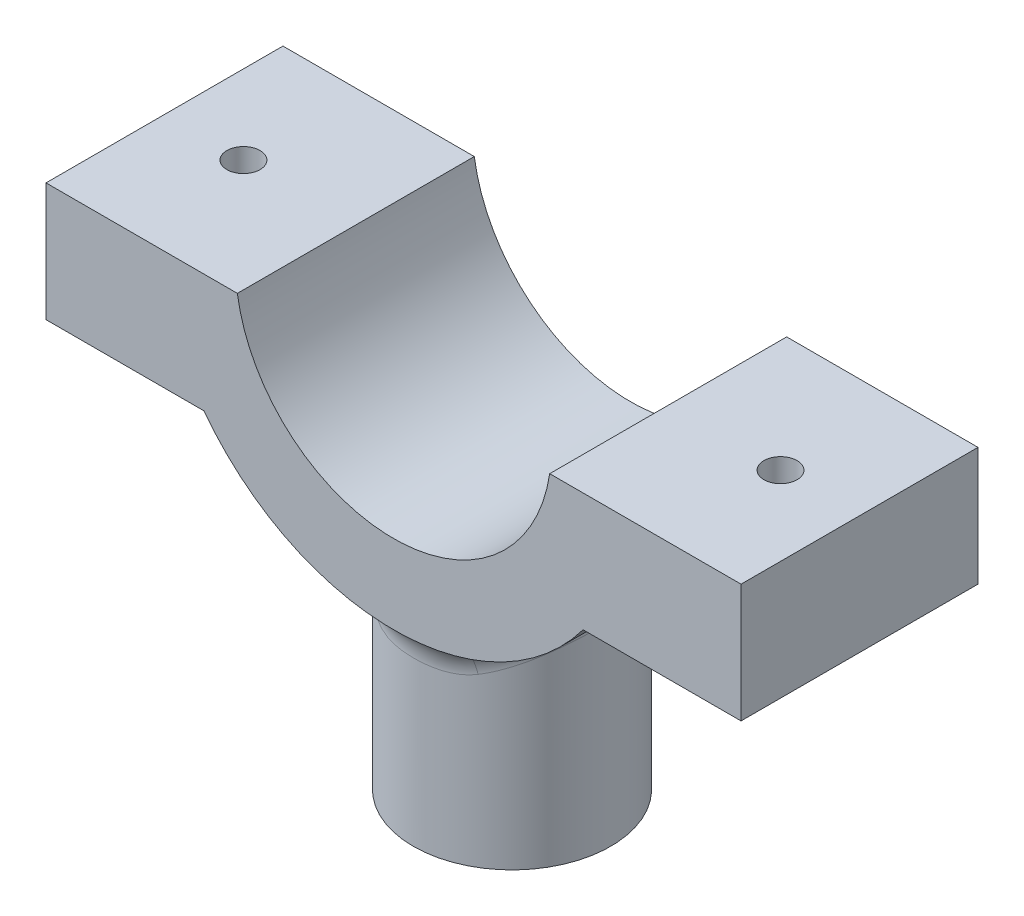
SolidWorks part; units mm, degrees
ref_plane "Plan de face" through (0, 0, 0) normal (0, 0, 1) x (1, 0, 0)
ref_plane "Plan de dessus" through (0, 0, 0) normal (0, 1, 0) x (1, 0, 0)
ref_plane "Plan de droite" through (0, 0, 0) normal (1, 0, 0) x (0, 0, -1)
sketch "Esquisse1" plane through (0, 0, 0) normal (0, 0, 1) x (1, 0, 0)
  line L0 (-19.7737, -3) -> (-44, -3)
  line L1 (-44, -3) -> (-44, -18)
  line L2 (-44, -18) -> (-24, -18)
  line L3 (19.7737, -3) -> (44, -3)
  line L4 (44, -3) -> (44, -18)
  line L5 (44, -18) -> (24, -18)
  line L8 (-44, 3) -> (-44, 18) construction
  line L9 (44, 3) -> (44, 18) construction
  arc A0 (-19.7737, -3) -> (19.7737, -3) centre (0, 0) ccw
  arc A1 (-24, -18) -> (24, -18) centre (0, 0) ccw
  circle A2 centre (0, 0) radius 20 construction
  point P9 (-16.333, -3)
  point P10 (-37.6154, -3)
  point P13 (0, 0)
  point P14 (28.954, -3)
  point P15 (0, 0)
  point P16 (0, 0)
  point P17 (0, 0)
  point P24 (0, 0)
  dimension "D2" = 10
  dimension "D1" = 15
  dimension "D3" = 3
extrude "Boss.-Extru.1" add sketch "Esquisse1" along normal mid plane 30 contours L0 L1 L2 A1 L5 L4 L3 A0
ref_plane "Plan1" through (0, -25, 0) normal (0, 1, 0) x (1, 0, 0)
sketch "Esquisse2" plane through (0, -25, 0) normal (0, 1, 0) x (1, 0, 0)
  circle A0 centre (0, 0) radius 12.5
  dimension "D1" = 25
extrude "Boss.-Extru.2" add sketch "Esquisse2" against normal blind 30
fillet "Congé1" radius 5 1 edges at (-1.7273, -29.9502, -12.3801)
hole_wizard "Trou taraudé M51" positions "Esquisse3" profile "Esquisse4" tap size "M5" standard "ISO" end condition through all
sketch "Esquisse3" plane through (0, -18, 0) normal (0, -1, 0) x (-1, 0, 0)
  line L0 (-44, -15) -> (-24, 15) construction
  line L2 (24, -15) -> (44, 15) construction
  point P0 (-34, 0)
  point P2 (34, 0)
  point P16 (0, 0)
  point P17 (0, 0)
sketch "Esquisse4" plane through (34, -18, 0) normal (1, 0, 0) x (0, 0, -1)
  line L0 (0, 0) -> (0, 15)
  line L1 (0, 15) -> (2.1, 15)
  line L2 (2.1, 15) -> (2.1, 0)
  line L5 (2.1, 0) -> (0, 0)
  line L11 (0, -6.35) -> (0, 107.95) construction
  dimension "Diamètre du trou pour taraudage jusqu'au prochain" = 4.2
  dimension "Profondeur du trou pour taraudage jusqu'au prochain" = 15
cosmetic thread "Filetage de perçage3" parameters "D1"=15, "D2"=5
cosmetic thread "Filetage de perçage4" parameters "D1"=15, "D2"=5
